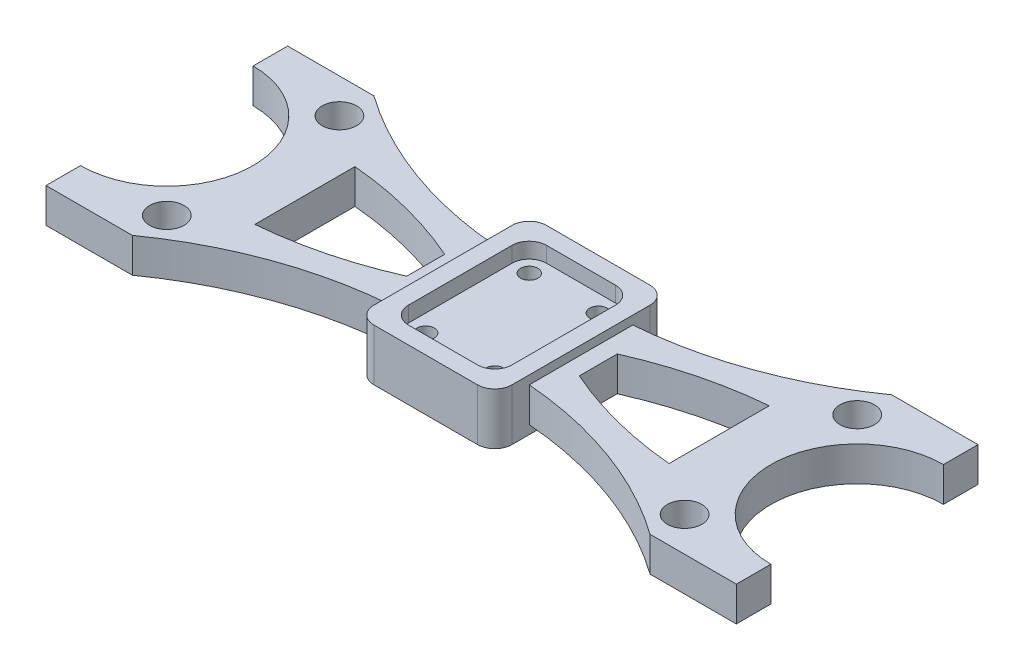
SolidWorks part; units mm, degrees
material "AISI 304"
ref_plane "Front Plane" through (0, 0, 0) normal (0, 0, 1) x (1, 0, 0)
ref_plane "Top Plane" through (0, 0, 0) normal (0, 1, 0) x (1, 0, 0)
ref_plane "Right Plane" through (0, 0, 0) normal (1, 0, 0) x (0, 0, -1)
sketch "Sketch1" plane through (0, 0, 0) normal (0, 1, 0) x (1, 0, 0)
  line L0 (0, 0) -> (63.2278, 0) construction
  line L1 (-10, 20) -> (10, 20)
  line L2 (-15, 15) -> (-15, -15)
  line L3 (-10, -20) -> (10, -20)
  line L4 (15, 15) -> (15, -15)
  line L5 (25, -5.5) -> (25, 5.5)
  line L6 (60, 14.5) -> (60, -14.5)
  line L7 (100, 25) -> (100, 35)
  line L8 (100, 35) -> (75, 35)
  line L9 (-15, 25) -> (15, 25)
  line L10 (20, 20) -> (20, -20)
  line L11 (-15, -25) -> (15, -25)
  line L12 (-20, 20) -> (-20, -20)
  line L13 (-20, 25) -> (-20, -25) construction
  line L14 (-20, 25) -> (20, 25) construction
  line L15 (20, 25) -> (20, -25) construction
  line L16 (-5, 20) -> (-5, -20) [skipped]
  line L17 (-5, -10) -> (-5, -50) [skipped]
  line L18 (15, -10) -> (15, -50) [skipped]
  line L19 (-20, -25) -> (20, -25) construction
  line L20 (-15, -20) -> (15, -20) construction
  line L21 (15, 20) -> (15, -20) construction
  line L22 (-15, 20) -> (-15, -20) construction
  line L23 (-15, 20) -> (15, 20) construction
  line L24 (100, -25) -> (100, -35)
  line L25 (100, -35) -> (75, -35)
  line L26 (0, 0) -> (0, 38.2925) construction
  line L27 (-100, -35) -> (-75, -35)
  line L28 (-100, -25) -> (-100, -35)
  line L29 (-60, 14.5) -> (-60, -14.5)
  line L30 (-25, -5.5) -> (-25, 5.5)
  line L31 (-100, 35) -> (-75, 35)
  line L32 (-100, 25) -> (-100, 35)
  arc A0 (25, 5.5) -> (60, 14.5) centre (69.5224, -95.0871) cw
  arc A1 (100, 25) -> (100, -25) centre (100, 0) ccw
  arc A2 (75, 35) -> (20, 15) centre (11.2627, 124.6525) cw
  circle A3 centre (10, 15) radius 2.5
  circle A4 centre (-10, 15) radius 2.5
  circle A5 centre (-10, -15) radius 2.5
  circle A6 centre (10, -15) radius 2.5
  arc A7 (-20, 20) -> (-15, 25) centre (-15, 20) cw
  arc A8 (15, 25) -> (20, 20) centre (15, 20) cw
  arc A9 (15, -25) -> (20, -20) centre (15, -20) ccw
  arc A10 (-15, -25) -> (-20, -20) centre (-15, -20) cw
  arc A11 (10, -20) -> (15, -15) centre (10, -15) ccw
  arc A12 (-10, -20) -> (-15, -15) centre (-10, -15) cw
  arc A13 (-15, 15) -> (-10, 20) centre (-10, 15) cw
  arc A14 (15, 15) -> (10, 20) centre (10, 15) ccw
  circle A15 centre (75, 25) radius 5
  arc A16 (25, -5.5) -> (60, -14.5) centre (69.5224, 95.0871) ccw
  circle A17 centre (75, -25) radius 5
  arc A18 (75, -35) -> (20, -15) centre (11.2627, -124.6525) ccw
  arc A19 (-75, -35) -> (-20, -15) centre (-11.2627, -124.6525) cw
  circle A20 centre (-75, -25) radius 5
  arc A21 (-25, 5.5) -> (-60, 14.5) centre (-69.5224, -95.0871) ccw
  arc A22 (-25, -5.5) -> (-60, -14.5) centre (-69.5224, 95.0871) cw
  circle A23 centre (-75, 25) radius 5
  arc A24 (-75, 35) -> (-20, 15) centre (-11.2627, 124.6525) ccw
  arc A25 (-100, 25) -> (-100, -25) centre (-100, 0) cw
  point P4 (0, 20)
  point P6 (15, 0)
  point P15 (60, 0)
  point P31 (-20, 25)
  point P56 (15, -20)
  point P76 (25, 0)
  dimension "D8" = 5
  dimension "D11" = 15
  dimension "D12" = 110
  dimension "50" = 50
  dimension "D18" = 5
  dimension "D20" = 10
  dimension "D22" = 110
  dimension "D2" = 40
  dimension "D3" = 50
  dimension "D6" = 30
  dimension "D7" = 20
  dimension "D9" = 10
  dimension "D10" = 15
  dimension "D13" = 5.5
  dimension "D14" = 14.5
  dimension "D15" = 10
  dimension "D16" = 25
  dimension "D17" = 35
  dimension "D19" = 65
  dimension "D21" = 25
  dimension "D1" = 5
  dimension "D4" = 2
  dimension "D5" = 2
extrude "Boss-Extrude1" add sketch "Sketch1" along normal mid plane 10 contours L32 A25 L28 L27 A19 L12 A24 L31 A23 A20 L30 A22 L29 A21 | A18 L25 L24 A1 L7 L8 A2 L10 A15 A16 L5 A0 L6 A17 region at (-63.5198, 0, 0) region at (63.5198, 0, 0)
extrude "Boss-Extrude2" add sketch "Sketch1<3>" along normal mid plane 6 separate body contours L4 A14 L1 A13 L2 A12 L3 A11 A3 A4 A5 A6 region at (-9.881, 0, 0) region at (4.6111, 0, 0)
sketch "Sketch1<3>" plane through (0, 0, 0) normal (0, 1, 0) x (1, 0, 0) same geometry as "Sketch1"
extrude "Boss-Extrude3" add sketch "Sketch1<4>" along normal mid plane 15 contours A10 L11 A9 L10 A8 L9 A7 L12 A14 L4 A11 L3 A12 L2 A13 L1 region at (-13.9883, 0, -18.9883) region at (5.4523, 0, 22.3158)
sketch "Sketch1<4>" plane through (0, 0, 0) normal (0, 1, 0) x (1, 0, 0) same geometry as "Sketch1"
